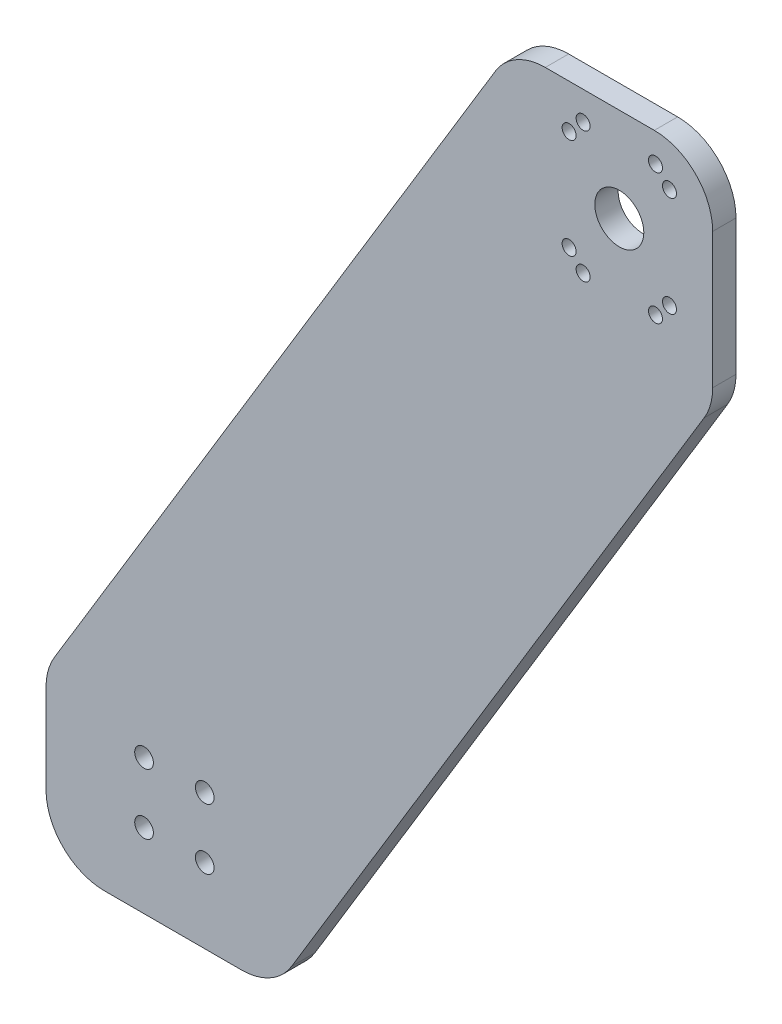
SolidWorks part; units mm, degrees
ref_plane "Piano frontale" through (0, 0, 0) normal (0, 0, 1) x (1, 0, 0)
ref_plane "Piano superiore" through (0, 0, 0) normal (0, 1, 0) x (1, 0, 0)
ref_plane "Piano destro" through (0, 0, 0) normal (1, 0, 0) x (0, 0, -1)
sketch "Schizzo1" plane through (0, 0, 0) normal (0, 0, 1) x (1, 0, 0)
  line L0 (25, 0) -> (83.8108, 0)
  line L1 (105.1949, 12.0493) -> (282.0244, 304.0295)
  line L2 (285.6403, 316.9801) -> (285.6403, 375)
  line L3 (260.6403, 400) -> (213.9419, 400)
  line L4 (0, 63.0199) -> (0, 25)
  line L5 (192.5578, 387.9507) -> (3.6159, 75.9705)
  line L6 (267.7327, 396.2552) -> (-16.2489, -72.6542) construction
  line L7 (14.2246, 45) -> (110.524, 45) construction
  line L8 (55.005, 45) -> (55.005, 90.084) construction
  line L9 (245.6403, 359.7762) -> (217.1497, 388.2668) construction
  line L10 (245.6403, 359.7762) -> (207.2912, 359.7762) construction
  line L11 (245.6403, 359.7762) -> (245.6403, 402.6918) construction
  line L13 (261.1403, 331.7762) -> (230.1403, 331.7762) construction
  line L14 (261.1403, 331.7762) -> (261.1403, 387.7762) construction
  line L15 (261.1403, 387.7762) -> (230.1403, 387.7762) construction
  line L16 (230.1403, 331.7762) -> (230.1403, 387.7762) construction
  line L17 (261.1403, 331.7762) -> (230.1403, 387.7762) construction
  line L18 (261.1403, 387.7762) -> (230.1403, 331.7762) construction
  circle A0 centre (42.005, 58) radius 4
  circle A1 centre (68.005, 58) radius 4
  circle A2 centre (68.005, 32) radius 4
  circle A3 centre (42.005, 32) radius 4
  circle A4 centre (245.6403, 359.7762) radius 10.5
  circle A5 centre (245.6403, 359.7762) radius 30.41 construction
  arc A6 (105.1949, 12.0493) -> (83.8108, 0) centre (83.8108, 25) cw
  arc A7 (25, 0) -> (0, 25) centre (25, 25) cw
  arc A8 (0, 63.0199) -> (3.6159, 75.9705) centre (25, 63.0199) cw
  arc A9 (285.6403, 316.9801) -> (282.0244, 304.0295) centre (260.6403, 316.9801) cw
  arc A10 (285.6403, 375) -> (260.6403, 400) centre (260.6403, 375) ccw
  arc A11 (213.9419, 400) -> (192.5578, 387.9507) centre (213.9419, 375) ccw
  circle A12 centre (230.1403, 387.7762) radius 3
  circle A13 centre (261.1403, 387.7762) radius 3
  circle A14 centre (267.1434, 381.2793) radius 3
  circle A15 centre (267.1434, 338.2731) radius 3
  circle A16 centre (261.1403, 331.7762) radius 3
  circle A17 centre (230.1403, 331.7762) radius 3
  circle A18 centre (224.1372, 338.2731) radius 3
  circle A19 centre (224.1372, 381.2793) radius 3
  point P27 (224.1372, 381.2793)
  point P28 (267.1434, 381.2793)
  point P29 (267.1434, 338.2731)
  point P30 (224.1372, 338.2731)
  point P39 (0, 0)
  point P42 (0, 70)
  point P45 (285.6403, 310)
  point P48 (285.6403, 400)
  dimension "D6" = 8
  dimension "D7" = 13
  dimension "D9" = 21
  dimension "D11" = 45
  dimension "D14" = 25
  dimension "D15" = 6
  dimension "D16" = 45
  dimension "D17" = 60.82
  dimension "D1" = 121.2
  dimension "D2" = 120
  dimension "D3" = 70
  dimension "D4" = 400
  dimension "D5" = 90
  dimension "D8" = 13
  dimension "D10" = 40
  dimension "D12" = 31
  dimension "D13" = 56
extrude "Estrusione-Estrusione2" add sketch "Schizzo1" against normal blind 10
sketch "Schizzo2" plane through (0, 0, 0) normal (0, -1, 0) x (1, 0, 0)
  line L0 (25, -5) -> (83.8108, -5) construction
  line L1 (25, -10) -> (25, 0) construction
  line L2 (83.8108, -10) -> (83.8108, 0) construction
  line L3 (54.4054, -5) -> (54.4054, 0) construction
  line L4 (25, 0) -> (83.8108, 0) construction
  circle A0 centre (54.4054, -5) radius 2
  circle A1 centre (81.9054, -5) radius 2
  circle A2 centre (26.9054, -5) radius 2
  dimension "D1" = 4
  dimension "D2" = 27.5
extrude "Taglio-Estrusione1" cut sketch "Schizzo2" against normal blind 15
